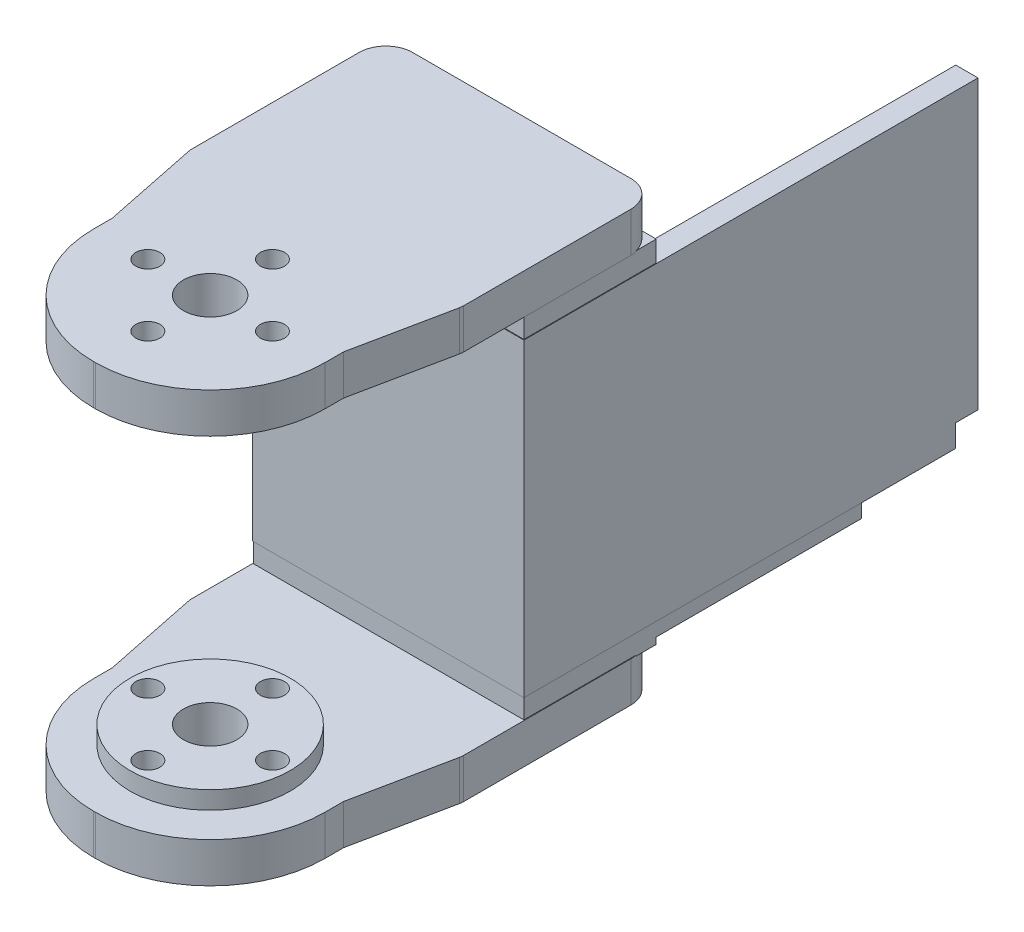
SolidWorks part; units mm, degrees
ref_plane "Front Plane" through (0, 0, 0) normal (0, 0, 1) x (1, 0, 0)
ref_plane "Top Plane" through (0, 0, 0) normal (0, 1, 0) x (1, 0, 0)
ref_plane "Right Plane" through (0, 0, 0) normal (1, 0, 0) x (0, 0, -1)
ref_plane "PY_p18_625" through (0, 18.625, 0) normal (0, 1, 0) x (1, 0, 0)
sketch "S_prism1" plane through (0, 18.625, 0) normal (0, 1, 0) x (1, 0, 0)
  line L0 (-13, 2) -> (-15.2191, 12.8008)
  line L1 (-15.26, 13.2033) -> (-15.26, 32)
  line L2 (-12.26, 35) -> (12.26, 35)
  line L3 (15.26, 32) -> (15.26, 13.2033)
  line L4 (15.2191, 12.8008) -> (13, 2)
  line L5 (13, 2) -> (13, -0.1)
  line L6 (0.1, -13) -> (-0.1, -13)
  line L7 (-13, -0.1) -> (-13, 2)
  arc A0 (-15.2191, 12.8008) -> (-15.26, 13.2033) centre (-13.2498, 13.2042) cw
  arc A1 (-15.26, 32) -> (-12.26, 35) centre (-12.2599, 31.9999) cw
  arc A2 (12.26, 35) -> (15.26, 32) centre (12.2599, 31.9999) cw
  arc A3 (15.26, 13.2033) -> (15.2191, 12.8008) centre (13.2498, 13.2042) cw
  arc A4 (13, -0.1) -> (0.1, -13) centre (0.1001, -0.1001) cw
  arc A5 (-0.1, -13) -> (-13, -0.1) centre (-0.1001, -0.1001) cw
extrude "Boss_1" add sketch "S_prism1" along normal blind 4.5
ref_plane "PY_m20_625" through (0, -20.625, 0) normal (0, 1, 0) x (1, 0, 0)
sketch "S_cyl2" plane through (0, -20.625, 0) normal (0, 1, 0) x (1, 0, 0)
  circle A0 centre (0, 0) radius 9
  dimension "D1_S_cyl2" = 18
extrude "Boss_2" add sketch "S_cyl2" along normal blind 2
ref_plane "PY_m25_125" through (0, -25.125, 0) normal (0, 1, 0) x (1, 0, 0)
sketch "S_prism3" plane through (0, -25.125, 0) normal (0, 1, 0) x (1, 0, 0)
  line L0 (-13, 2) -> (-15.2191, 12.8008)
  line L1 (-15.26, 13.2033) -> (-15.26, 32)
  line L2 (-12.26, 35) -> (12.26, 35)
  line L3 (15.26, 32) -> (15.26, 13.2033)
  line L4 (15.2191, 12.8008) -> (13, 2)
  line L5 (13, 2) -> (13, -0.1)
  line L6 (0.1, -13) -> (-0.1, -13)
  line L7 (-13, -0.1) -> (-13, 2)
  arc A0 (-15.2191, 12.8008) -> (-15.26, 13.2033) centre (-13.2498, 13.2042) cw
  arc A1 (-15.26, 32) -> (-12.26, 35) centre (-12.2599, 31.9999) cw
  arc A2 (12.26, 35) -> (15.26, 32) centre (12.2599, 31.9999) cw
  arc A3 (15.26, 13.2033) -> (15.2191, 12.8008) centre (13.2498, 13.2042) cw
  arc A4 (13, -0.1) -> (0.1, -13) centre (0.1001, -0.1001) cw
  arc A5 (-0.1, -13) -> (-13, -0.1) centre (-0.1001, -0.1001) cw
extrude "Boss_3" add sketch "S_prism3" along normal blind 4.5
ref_plane "PZ_m22_490" through (0, 0, -22.49) normal (0, 0, 1) x (1, 0, 0)
sketch "S_box4" plane through (0, 0, -22.49) normal (0, 0, 1) x (1, 0, 0)
  line L0 (-15.26, -18.4) -> (15.26, -18.4)
  line L1 (15.26, -18.4) -> (15.26, 16.4)
  line L2 (15.26, 16.4) -> (-15.26, 16.4)
  line L3 (-15.26, 16.4) -> (-15.26, -18.4)
  dimension "P1" = 15.26
  dimension "P2" = 18.4
  dimension "P3" = 15.26
  dimension "P4" = 18.4
  dimension "P5" = 15.26
  dimension "P6" = 16.4
  dimension "P7" = 15.26
  dimension "P8" = 16.4
extrude "Boss_4" add sketch "S_box4" along normal blind 2.5
ref_plane "PZ_m71_010" through (0, 0, -71.01) normal (0, 0, 1) x (1, 0, 0)
sketch "S_box5" plane through (0, 0, -71.01) normal (0, 0, 1) x (1, 0, 0)
  line L0 (12.76, -18.4) -> (15.26, -18.4)
  line L1 (15.26, -18.4) -> (15.26, 16.4)
  line L2 (15.26, 16.4) -> (12.76, 16.4)
  line L3 (12.76, 16.4) -> (12.76, -18.4)
  dimension "P1" = 12.76
  dimension "P2" = 18.4
  dimension "P3" = 15.26
  dimension "P4" = 18.4
  dimension "P5" = 15.26
  dimension "P6" = 16.4
  dimension "P7" = 12.76
  dimension "P8" = 16.4
extrude "Boss_5" add sketch "S_box5" along normal blind 51.02
sketch "S_box6" plane through (0, 0, -71.01) normal (0, 0, 1) x (1, 0, 0)
  line L0 (-15.26, -18.4) -> (15.26, -18.4)
  line L1 (15.26, -18.4) -> (15.26, -16)
  line L2 (15.26, -16) -> (-15.26, -16)
  line L3 (-15.26, -16) -> (-15.26, -18.4)
  dimension "P1" = 15.26
  dimension "P2" = 18.4
  dimension "P3" = 15.26
  dimension "P4" = 18.4
  dimension "P5" = 15.26
  dimension "P6" = 16
  dimension "P7" = 15.26
  dimension "P8" = 16
extrude "Boss_6" add sketch "S_box6" along normal blind 51.02
ref_plane "PZ_m38_000" through (0, 0, -38) normal (0, 0, 1) x (1, 0, 0)
sketch "S_box7" plane through (0, 0, -38) normal (0, 0, 1) x (1, 0, 0)
  line L0 (-15.26, -18.4) -> (-12.76, -18.4)
  line L1 (-12.76, -18.4) -> (-12.76, 16.4)
  line L2 (-12.76, 16.4) -> (-15.26, 16.4)
  line L3 (-15.26, 16.4) -> (-15.26, -18.4)
  dimension "P1" = 15.26
  dimension "P2" = 18.4
  dimension "P3" = 12.76
  dimension "P4" = 18.4
  dimension "P5" = 12.76
  dimension "P6" = 16.4
  dimension "P7" = 15.26
  dimension "P8" = 16.4
extrude "Boss_7" add sketch "S_box7" along normal blind 18.01
ref_plane "PZ_m34_930" through (0, 0, -34.93) normal (0, 0, 1) x (1, 0, 0)
sketch "S_box8" plane through (0, 0, -34.93) normal (0, 0, 1) x (1, 0, 0)
  line L0 (-15.19, 16.05) -> (15.19, 16.05)
  line L1 (15.19, 16.05) -> (15.19, 18.725)
  line L2 (15.19, 18.725) -> (-15.19, 18.725)
  line L3 (-15.19, 18.725) -> (-15.19, 16.05)
  dimension "P1" = 15.19
  dimension "P2" = 16.05
  dimension "P3" = 15.19
  dimension "P4" = 16.05
  dimension "P5" = 15.19
  dimension "P6" = 18.725
  dimension "P7" = 15.19
  dimension "P8" = 18.725
extrude "Boss_8" add sketch "S_box8" along normal blind 14.87
sketch "S_box9" plane through (0, 0, -34.93) normal (0, 0, 1) x (1, 0, 0)
  line L0 (-15.19, -20.725) -> (15.19, -20.725)
  line L1 (15.19, -20.725) -> (15.19, -18.3)
  line L2 (15.19, -18.3) -> (-15.19, -18.3)
  line L3 (-15.19, -18.3) -> (-15.19, -20.725)
  dimension "P1" = 15.19
  dimension "P2" = 20.725
  dimension "P3" = 15.19
  dimension "P4" = 20.725
  dimension "P5" = 15.19
  dimension "P6" = 18.3
  dimension "P7" = 15.19
  dimension "P8" = 18.3
extrude "Boss_9" add sketch "S_box9" along normal blind 14.87
ref_plane "PZ_m58_000" through (0, 0, -58) normal (0, 0, 1) x (1, 0, 0)
sketch "S_box10" plane through (0, 0, -58) normal (0, 0, 1) x (1, 0, 0)
  line L0 (-15.19, -20) -> (15.19, -20)
  line L1 (15.19, -20) -> (15.19, -18.35)
  line L2 (15.19, -18.35) -> (-15.19, -18.35)
  line L3 (-15.19, -18.35) -> (-15.19, -20)
  dimension "P1" = 15.19
  dimension "P2" = 20
  dimension "P3" = 15.19
  dimension "P4" = 20
  dimension "P5" = 15.19
  dimension "P6" = 18.35
  dimension "P7" = 15.19
  dimension "P8" = 18.35
extrude "Boss_10" add sketch "S_box10" along normal blind 37.94
ref_plane "PY_p18_525" through (0, 18.525, 0) normal (0, 1, 0) x (1, 0, 0)
sketch "S_hole11" plane through (0, 18.525, 0) normal (0, 1, 0) x (1, 0, 0)
  circle A0 centre (0, 0) radius 3
  dimension "D1_S_hole11" = 6
extrude "Hole_11" cut sketch "S_hole11" along normal blind 4.7
sketch "S_hole12" plane through (0, 18.525, 0) normal (0, 1, 0) x (1, 0, 0)
  circle A0 centre (7, 0) radius 1.35
  dimension "D1_S_hole12" = 2.7
  dimension "P2" = 7
extrude "Hole_12" cut sketch "S_hole12" along normal blind 4.7
sketch "S_hole13" plane through (0, 18.525, 0) normal (0, 1, 0) x (1, 0, 0)
  circle A0 centre (0, -7) radius 1.35
  dimension "D1_S_hole13" = 2.7
  dimension "P2" = 7
extrude "Hole_13" cut sketch "S_hole13" along normal blind 4.7
sketch "S_hole14" plane through (0, 18.525, 0) normal (0, 1, 0) x (1, 0, 0)
  circle A0 centre (-7, 0) radius 1.35
  dimension "D1_S_hole14" = 2.7
  dimension "P2" = 7
extrude "Hole_14" cut sketch "S_hole14" along normal blind 4.7
sketch "S_hole15" plane through (0, 18.525, 0) normal (0, 1, 0) x (1, 0, 0)
  circle A0 centre (0, 7) radius 1.35
  dimension "D1_S_hole15" = 2.7
  dimension "P2" = 7
extrude "Hole_15" cut sketch "S_hole15" along normal blind 4.7
ref_plane "PY_m25_225" through (0, -25.225, 0) normal (0, 1, 0) x (1, 0, 0)
sketch "S_hole16" plane through (0, -25.225, 0) normal (0, 1, 0) x (1, 0, 0)
  circle A0 centre (0, 0) radius 3
  dimension "D1_S_hole16" = 6
extrude "Hole_16" cut sketch "S_hole16" along normal blind 6.7
sketch "S_hole17" plane through (0, -25.225, 0) normal (0, 1, 0) x (1, 0, 0)
  circle A0 centre (7, 0) radius 1.35
  dimension "D1_S_hole17" = 2.7
  dimension "P2" = 7
extrude "Hole_17" cut sketch "S_hole17" along normal blind 6.7
sketch "S_hole18" plane through (0, -25.225, 0) normal (0, 1, 0) x (1, 0, 0)
  circle A0 centre (0, -7) radius 1.35
  dimension "D1_S_hole18" = 2.7
  dimension "P2" = 7
extrude "Hole_18" cut sketch "S_hole18" along normal blind 6.7
sketch "S_hole19" plane through (0, -25.225, 0) normal (0, 1, 0) x (1, 0, 0)
  circle A0 centre (-7, 0) radius 1.35
  dimension "D1_S_hole19" = 2.7
  dimension "P2" = 7
extrude "Hole_19" cut sketch "S_hole19" along normal blind 6.7
sketch "S_hole20" plane through (0, -25.225, 0) normal (0, 1, 0) x (1, 0, 0)
  circle A0 centre (0, 7) radius 1.35
  dimension "D1_S_hole20" = 2.7
  dimension "P2" = 7
extrude "Hole_20" cut sketch "S_hole20" along normal blind 6.7
ref_plane "PY_m18_500" through (0, -18.5, 0) normal (0, 1, 0) x (1, 0, 0)
sketch "S_hole21" plane through (0, -18.5, 0) normal (0, 1, 0) x (1, 0, 0)
  circle A0 centre (0, 58) radius 11
  dimension "D1_S_hole21" = 22
  dimension "P2" = 58
extrude "Hole_21" cut sketch "S_hole21" along normal blind 2.6
sketch "S_hole22" plane through (0, -18.5, 0) normal (0, 1, 0) x (1, 0, 0)
  circle A0 centre (-10.25, 49.7) radius 1.1
  dimension "D1_S_hole22" = 2.2
  dimension "P2" = 10.25
  dimension "P3" = 49.7
extrude "Hole_22" cut sketch "S_hole22" along normal blind 2.6
sketch "S_hole23" plane through (0, -18.5, 0) normal (0, 1, 0) x (1, 0, 0)
  circle A0 centre (10.25, 49.7) radius 1.1
  dimension "D1_S_hole23" = 2.2
  dimension "P2" = 10.25
  dimension "P3" = 49.7
extrude "Hole_23" cut sketch "S_hole23" along normal blind 2.6
sketch "S_hole24" plane through (0, -18.5, 0) normal (0, 1, 0) x (1, 0, 0)
  circle A0 centre (-10.25, 25.25) radius 1.1
  dimension "D1_S_hole24" = 2.2
  dimension "P2" = 10.25
  dimension "P3" = 25.25
extrude "Hole_24" cut sketch "S_hole24" along normal blind 2.6
sketch "S_hole25" plane through (0, -18.5, 0) normal (0, 1, 0) x (1, 0, 0)
  circle A0 centre (10.25, 25.25) radius 1.1
  dimension "D1_S_hole25" = 2.2
  dimension "P2" = 10.25
  dimension "P3" = 25.25
extrude "Hole_25" cut sketch "S_hole25" along normal blind 2.6
ref_plane "PZ_m71_110" through (0, 0, -71.11) normal (0, 0, 1) x (1, 0, 0)
sketch "S_cut26" plane through (0, 0, -71.11) normal (0, 0, 1) x (1, 0, 0)
  line L0 (-15.36, -18.5) -> (15.36, -18.5)
  line L1 (15.36, -18.5) -> (15.36, -15.9)
  line L2 (15.36, -15.9) -> (-15.36, -15.9)
  line L3 (-15.36, -15.9) -> (-15.36, -18.5)
  dimension "P1" = 15.36
  dimension "P2" = 18.5
  dimension "P3" = 15.36
  dimension "P4" = 18.5
  dimension "P5" = 15.36
  dimension "P6" = 15.9
  dimension "P7" = 15.36
  dimension "P8" = 15.9
extrude "Pocket_26" cut sketch "S_cut26" along normal blind 2.6
sketch "S_hole27" plane through (0, -25.225, 0) normal (0, 1, 0) x (1, 0, 0)
  circle A0 centre (-10.25, 25.25) radius 2.5
  dimension "D1_S_hole27" = 5
  dimension "P2" = 10.25
  dimension "P3" = 25.25
extrude "Hole_27" cut sketch "S_hole27" along normal blind 5.175
sketch "S_hole28" plane through (0, -25.225, 0) normal (0, 1, 0) x (1, 0, 0)
  circle A0 centre (10.25, 25.25) radius 2.5
  dimension "D1_S_hole28" = 5
  dimension "P2" = 10.25
  dimension "P3" = 25.25
extrude "Hole_28" cut sketch "S_hole28" along normal blind 5.175
ref_plane "PY_m20_100" through (0, -20.1, 0) normal (0, 1, 0) x (1, 0, 0)
sketch "S_hole29" plane through (0, -20.1, 0) normal (0, 1, 0) x (1, 0, 0)
  circle A0 centre (0, 58) radius 11
  dimension "D1_S_hole29" = 22
  dimension "P2" = 58
extrude "Hole_29" cut sketch "S_hole29" along normal blind 1.8
sketch "S_hole30" plane through (0, -20.1, 0) normal (0, 1, 0) x (1, 0, 0)
  circle A0 centre (-10.25, 49.7) radius 1.1
  dimension "D1_S_hole30" = 2.2
  dimension "P2" = 10.25
  dimension "P3" = 49.7
extrude "Hole_30" cut sketch "S_hole30" along normal blind 1.8
sketch "S_hole31" plane through (0, -20.1, 0) normal (0, 1, 0) x (1, 0, 0)
  circle A0 centre (-10.25, 49.7) radius 2.1
  dimension "D1_S_hole31" = 4.2
  dimension "P2" = 10.25
  dimension "P3" = 49.7
extrude "Hole_31" cut sketch "S_hole31" along normal blind 1.7
sketch "S_hole32" plane through (0, -20.1, 0) normal (0, 1, 0) x (1, 0, 0)
  circle A0 centre (10.25, 49.7) radius 1.1
  dimension "D1_S_hole32" = 2.2
  dimension "P2" = 10.25
  dimension "P3" = 49.7
extrude "Hole_32" cut sketch "S_hole32" along normal blind 1.8
sketch "S_hole33" plane through (0, -20.1, 0) normal (0, 1, 0) x (1, 0, 0)
  circle A0 centre (10.25, 49.7) radius 2.1
  dimension "D1_S_hole33" = 4.2
  dimension "P2" = 10.25
  dimension "P3" = 49.7
extrude "Hole_33" cut sketch "S_hole33" along normal blind 1.7
sketch "S_hole34" plane through (0, -20.1, 0) normal (0, 1, 0) x (1, 0, 0)
  circle A0 centre (-10.25, 25.25) radius 1.1
  dimension "D1_S_hole34" = 2.2
  dimension "P2" = 10.25
  dimension "P3" = 25.25
extrude "Hole_34" cut sketch "S_hole34" along normal blind 1.8
sketch "S_hole35" plane through (0, -20.1, 0) normal (0, 1, 0) x (1, 0, 0)
  circle A0 centre (-10.25, 25.25) radius 2.1
  dimension "D1_S_hole35" = 4.2
  dimension "P2" = 10.25
  dimension "P3" = 25.25
extrude "Hole_35" cut sketch "S_hole35" along normal blind 1.7
sketch "S_hole36" plane through (0, -20.1, 0) normal (0, 1, 0) x (1, 0, 0)
  circle A0 centre (10.25, 25.25) radius 1.1
  dimension "D1_S_hole36" = 2.2
  dimension "P2" = 10.25
  dimension "P3" = 25.25
extrude "Hole_36" cut sketch "S_hole36" along normal blind 1.8
sketch "S_hole37" plane through (0, -20.1, 0) normal (0, 1, 0) x (1, 0, 0)
  circle A0 centre (10.25, 25.25) radius 2.1
  dimension "D1_S_hole37" = 4.2
  dimension "P2" = 10.25
  dimension "P3" = 25.25
extrude "Hole_37" cut sketch "S_hole37" along normal blind 1.7
equation "\"plate_t\" = 3"
equation "\"clearance\" = 0.4"
